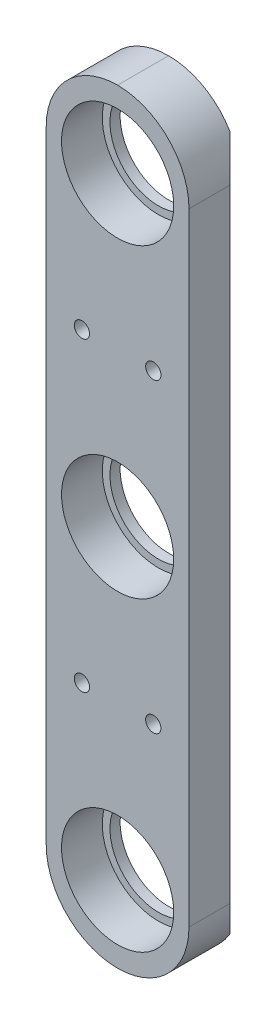
SolidWorks part; units mm, degrees
ref_plane "Alzado" through (0, 0, 0) normal (1, 0, 0) x (0, 1, 0)
ref_plane "Planta" through (0, 0, 0) normal (0, 0, 1) x (0, 1, 0)
ref_plane "Vista lateral" through (0, 0, 0) normal (0, 1, 0) x (-1, 0, 0)
sketch "Croquis1" plane through (0, 0, 0) normal (0, 0, 1) x (0, 1, 0)
  line L1 (75, 14) -> (-75, 14)
  line L2 (75, 14) -> (75, -14)
  line L3 (75, -14) -> (-75, -14)
  line L4 (-75, 14) -> (-75, -14)
  line L5 (0, -14) -> (0, 14) construction
  line L6 (75, 0) -> (-75, 0) construction
  circle A0 centre (0, 0) radius 11
  circle A1 centre (60, 0) radius 11
  circle A2 centre (-60, 0) radius 11
  point P0 (0, 0)
  dimension "D3" = 22
  dimension "D1" = 28
  dimension "D2" = 150
  dimension "D4" = 2
  dimension "D5" = 2
extrude "Saliente-Extruir1" add sketch "Croquis1" along normal blind 10
sketch "Croquis2" plane through (0, 0, 0) normal (0, 0, 1) x (0, 1, 0)
  line L1 (-75, 14) -> (75, 14)
  line L2 (-75, 14) -> (-75, -14)
  line L3 (-75, -14) -> (75, -14)
  line L4 (75, 14) -> (75, -14)
  circle A0 centre (0, 0) radius 9.5
  circle A1 centre (60, 0) radius 9.5
  circle A2 centre (-60, 0) radius 9.5
  dimension "D1" = 19
  dimension "D2" = 2
  dimension "D3" = 2
extrude "Saliente-Extruir2" add sketch "Croquis2" along normal blind 2
chamfer "Chaflán1" distance 2 angle 45 1 edges at (14, 0, 0)
fillet "Redondeo1" radius 14 4 edges at (14, 75, 6) (-14, 75, 5) (14, -75, 6) (-14, -75, 5)
sketch "Croquis3" plane through (0, 0, 10) normal (0, 0, 1) x (1, 0, 0)
  line L0 (-14, 0) -> (14, 0) construction
  line L1 (-14, 61) -> (-14, -61) construction
  line L2 (14, -61) -> (14, 61) construction
  line L3 (0, 0) -> (0, 30) construction
  line L4 (0, 30) -> (-7, 30) construction
  circle A0 centre (-7, 30) radius 1.5
  circle A1 centre (7, 30) radius 1.5
  circle A2 centre (7, -30) radius 1.5
  circle A3 centre (-7, -30) radius 1.5
  dimension "D3" = 3
  dimension "D1" = 30
  dimension "D2" = 7
extrude "Cortar-Extruir1" cut sketch "Croquis3" against normal up to next
